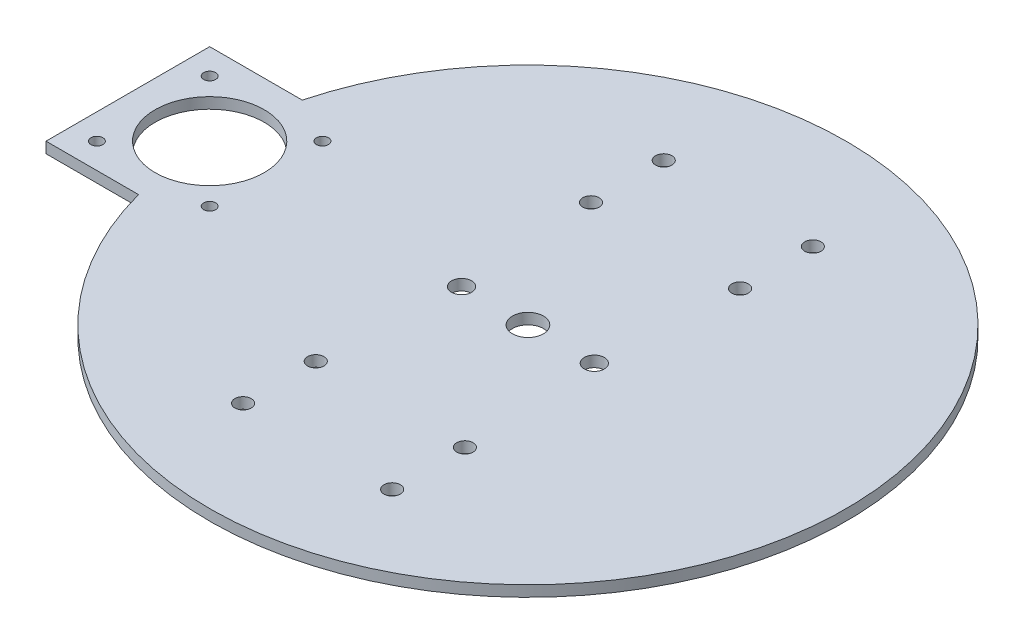
SolidWorks part; units mm, degrees
ref_plane "Front Plane" through (0, 0, 0) normal (0, 0, 1) x (1, 0, 0)
ref_plane "Top Plane" through (0, 0, 0) normal (0, 1, 0) x (1, 0, 0)
ref_plane "Right Plane" through (0, 0, 0) normal (1, 0, 0) x (0, 0, -1)
sketch "Sketch2" plane through (0, 0, 0) normal (0, 1, 0) x (1, 0, 0)
  line L0 (0, 87.5) -> (0, -87.5) construction
  line L1 (-110, 22.5) -> (-65, 22.5)
  line L2 (-110, 22.5) -> (-110, -22.5)
  line L3 (-110, -22.5) -> (-65, -22.5)
  line L4 (-65, 22.5) -> (-65, -22.5) construction
  line L5 (-110, 22.5) -> (-65, -22.5) construction
  line L6 (-110, -22.5) -> (-65, 22.5) construction
  line L7 (-66.5, -21) -> (-108.5, -21) construction
  line L8 (-66.5, -21) -> (-66.5, 21) construction
  line L9 (-66.5, 21) -> (-108.5, 21) construction
  line L10 (-108.5, -21) -> (-108.5, 21) construction
  line L11 (-66.5, -21) -> (-108.5, 21) construction
  line L12 (-66.5, 21) -> (-108.5, -21) construction
  line L13 (-87.5, 0) -> (87.5, 0) construction
  line L18 (0, 0) -> (-2.0021, 3.7489)
  line L19 (-27.269, 51.0612) -> (-27.7935, 52.0434)
  line L20 (0, 0) -> (2.0021, 3.7489)
  line L21 (27.269, 51.0612) -> (27.7935, 52.0434)
  line L22 (0, 0) -> (2.0021, -3.7489)
  line L23 (27.269, -51.0612) -> (27.7935, -52.0434)
  line L24 (-27.269, -51.0612) -> (-27.7935, -52.0434)
  line L25 (0, 0) -> (-2.0021, -3.7489)
  line L26 (-25.4381, 47.633) -> (-27.269, 51.0612)
  line L27 (25.4381, 47.633) -> (27.269, 51.0612)
  line L32 (-25.4381, -47.633) -> (-27.269, -51.0612)
  line L33 (25.4381, -47.633) -> (27.269, -51.0612)
  circle A0 centre (0, 0) radius 78.75 construction
  circle A2 centre (-87.5, 0) radius 8.75 construction
  circle A3 centre (0, 0) radius 87.5
  circle A4 centre (-87.5, 0) radius 15
  circle A5 centre (-103, 15.5) radius 1.65
  circle A6 centre (-72, 15.5) radius 1.65
  circle A7 centre (-72, -15.5) radius 1.65
  circle A8 centre (-103, -15.5) radius 1.65
  arc A9 (-27.7935, 52.0434) -> (-27.7935, -52.0434) centre (0, 0) ccw
  arc A10 (-25.4381, 47.633) -> (-25.4381, -47.633) centre (0, 0) ccw
  circle A11 centre (0, 0) radius 4.25
  circle A12 centre (18.25, 0) radius 2.75
  circle A13 centre (-18.25, 0) radius 2.75
  circle A14 centre (-20.5, 57.8302) radius 2.25
  circle A15 centre (20.5, 57.8302) radius 2.25
  circle A16 centre (20.5, 37.8302) radius 2.25
  circle A17 centre (-20.5, 37.8302) radius 2.25
  circle A18 centre (-20.5, -37.8302) radius 2.25
  circle A19 centre (20.5, -37.8302) radius 2.25
  circle A20 centre (20.5, -57.8302) radius 2.25
  circle A21 centre (-20.5, -57.8302) radius 2.25
  circle A22 centre (-20.5, 57.8302) radius 4
  circle A23 centre (20.5, 57.8302) radius 4
  circle A24 centre (-20.5, -57.8302) radius 4
  circle A25 centre (20.5, -57.8302) radius 4
  arc A29 (25.4381, -47.633) -> (25.4381, 47.633) centre (0, 0) ccw
  arc A31 (27.7935, -52.0434) -> (27.7935, 52.0434) centre (0, 0) ccw
  point P32 (0, 47.8302)
  point P55 (0, -47.8302)
  dimension "D1" = 175
  dimension "D2" = 157.5
  dimension "D3" = 45
  dimension "D5" = 17.5
  dimension "D6" = 5.5
  dimension "D10" = 18.25
  dimension "D11" = 36.5
  dimension "D14" = 2
  dimension "D4" = 45
  dimension "D7" = 42
  dimension "D8" = 2
  dimension "D9" = 2
  dimension "D15" = 2
extrude "Boss-Extrude3" add sketch "Sketch2" along normal blind 3 contours A4 A3 L1 L2 L3 A8 A5 | A4 A3 A31 L23 L33 A29 L27 L21 A25 A24 A23 A22 A18 A17 A16 A13 A12 A11 A7 A6 L26 A10 L32 L24 A9 L19 A19 | L23 A31 L21 L27 A29 L33 | A10 L26 L19 A9 L24 L32 | A25 A20 | A14 | A15 | A24 A21 | A22 | A23 region at (-97.2788, 0, -21.9831) region at (11.0261, 0, -84.3163) region at (-27.3183, 0, -48.8319) region at (28.4959, 0, -51.0371) region at (-20.5, 0, -57.8302) region at (20.5, 0, -57.8302) region at (-24.3869, 0, 57.8302) region at (16.6131, 0, 57.8302)
